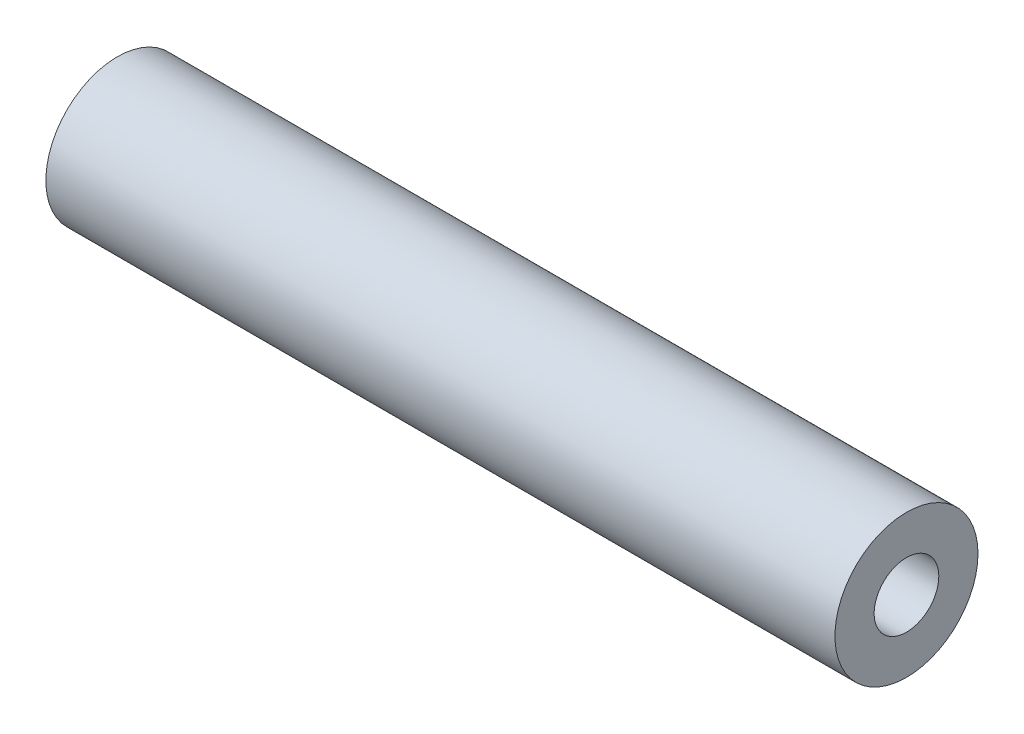
SolidWorks part; units mm, degrees
ref_plane "Front Plane" through (0, 0, 0) normal (0, 0, 1) x (1, 0, 0)
ref_plane "Top Plane" through (0, 0, 0) normal (0, 1, 0) x (1, 0, 0)
ref_plane "Right Plane" through (0, 0, 0) normal (1, 0, 0) x (0, 0, -1)
sketch "Sketch1" plane through (0, 0, 0) normal (1, 0, 0) x (0, 0, -1)
  circle A0 centre (0, 0) radius 4.7625
  circle A1 centre (0, 0) radius 2.1526
  dimension "D1" = 9.525
  dimension "D2" = 4.3053
extrude "Boss-Extrude1" add sketch "Sketch1" along normal blind 52.5399
